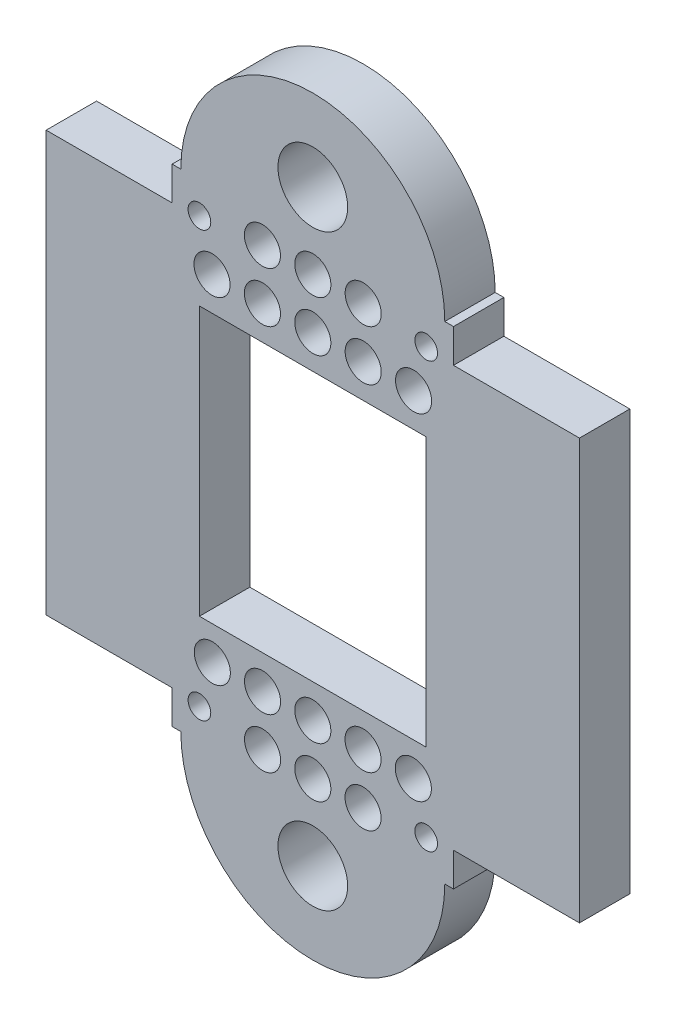
SolidWorks part; units mm, degrees
ref_plane "Front Plane" through (0, 0, 0) normal (0, 0, 1) x (1, 0, 0)
ref_plane "Top Plane" through (0, 0, 0) normal (0, 1, 0) x (1, 0, 0)
ref_plane "Right Plane" through (0, 0, 0) normal (1, 0, 0) x (0, 0, -1)
sketch "Sketch1" plane through (0, 0, 0) normal (0, 0, 1) x (1, 0, 0)
  line L0 (-13.5, -16) -> (13.5, -16)
  line L1 (-16.75, 29) -> (-15.7154, 29)
  line L2 (-16.75, 29) -> (-16.75, 25)
  line L3 (-16.75, -29) -> (-15.7154, -29)
  line L4 (16.75, 29) -> (16.75, 25)
  line L5 (-13.5, 16) -> (13.5, 16)
  line L6 (-13.5, 16) -> (-13.5, -16)
  line L8 (13.5, 16) -> (13.5, -16)
  line L9 (31.75, 25) -> (31.75, -25)
  line L10 (0, 0) -> (0, 6.7852) construction
  line L11 (31.75, 25) -> (16.75, 25)
  line L13 (31.75, -25) -> (16.75, -25)
  line L14 (-19.5, 29.3) -> (19.5, 29.3) construction
  line L15 (-19.5, 29.3) -> (-19.5, -29.3) construction
  line L16 (-19.5, -29.3) -> (19.5, -29.3) construction
  line L17 (19.5, 29.3) -> (19.5, -29.3) construction
  line L18 (-31.75, -25) -> (-16.75, -25)
  line L19 (-31.75, 25) -> (-16.75, 25)
  line L20 (0, 0) -> (4.3335, 0) construction
  line L21 (15.7154, 29) -> (16.75, 29)
  line L22 (15.7154, -29) -> (16.75, -29)
  line L23 (-31.75, 25) -> (-31.75, -25)
  line L24 (-16.75, -25) -> (-16.75, -29)
  line L25 (16.75, -25) -> (16.75, -29)
  circle A2 centre (-13.5, 25.3) radius 1.35
  circle A4 centre (13.5, -25.3) radius 1.35
  circle A5 centre (-13.5, -25.3) radius 1.35
  circle A6 centre (13.5, 25.3) radius 1.35
  circle A8 centre (0, 35) radius 4.15
  circle A13 centre (0, -35) radius 4.15
  arc A16 (-15.7154, 29) -> (15.7154, 29) centre (0, 29) cw
  arc A17 (-15.7154, -29) -> (15.7154, -29) centre (0, -29) ccw
  point P11 (0, 16)
  point P12 (-13.5, 0)
  point P29 (19.5, 0)
  point P30 (0, 29.3)
  dimension "D8" = 2.7
  dimension "D22" = 8.3
  dimension "D23" = 6
  dimension "D1" = 27
  dimension "D2" = 33.5
  dimension "D3" = 58
  dimension "D4" = 32
  dimension "D5" = 4
  dimension "D6" = 4
  dimension "D7" = 15
  dimension "D9" = 58.6
  dimension "D10" = 39
  dimension "D11" = 6
  dimension "D12" = 4
  dimension "D13" = 4
  dimension "D14" = 6
  dimension "D15" = 6
  dimension "D16" = 6
  dimension "D17" = 4
  dimension "D18" = 4
extrude "Boss-Extrude1" add sketch "Sketch1" along normal blind 6
sketch "Sketch2" plane through (0, 0, 6) normal (0, 0, 1) x (1, 0, 0)
  line L3 (13.5, 16) -> (-13.5, 16) construction
  line L4 (-13.5, -16) -> (13.5, -16) construction
  circle A0 centre (-12, 20) radius 2.15
  circle A1 centre (-6, 20) radius 2.15
  circle A2 centre (0, 20) radius 2.15
  circle A3 centre (6, 20) radius 2.15
  circle A4 centre (12, 20) radius 2.15
  circle A5 centre (-6, 26) radius 2.15
  circle A6 centre (0, 26) radius 2.15
  circle A7 centre (6, 26) radius 2.15
  circle A8 centre (-11.9673, -20) radius 2.15
  circle A9 centre (-5.9837, -20) radius 2.15
  circle A10 centre (0, -20) radius 2.15
  circle A11 centre (5.9837, -20) radius 2.15
  circle A12 centre (11.9673, -20) radius 2.15
  circle A13 centre (-5.9837, -26) radius 2.15
  circle A14 centre (0, -26) radius 2.15
  circle A15 centre (5.9837, -26) radius 2.15
  dimension "D1" = 4.3
  dimension "D5" = 4.3
  dimension "D11" = 4.3
  dimension "D12" = 4.3
  dimension "D13" = 4.3
  dimension "D14" = 4.3
  dimension "D15" = 4.3
  dimension "D16" = 4.3
  dimension "D2" = 4
  dimension "D3" = 4
  dimension "D6" = 6
  dimension "D10" = 6
  dimension "D4" = 5
  dimension "D9" = 5
extrude "Cut-Extrude1" cut sketch "Sketch2" against normal blind 4.2
